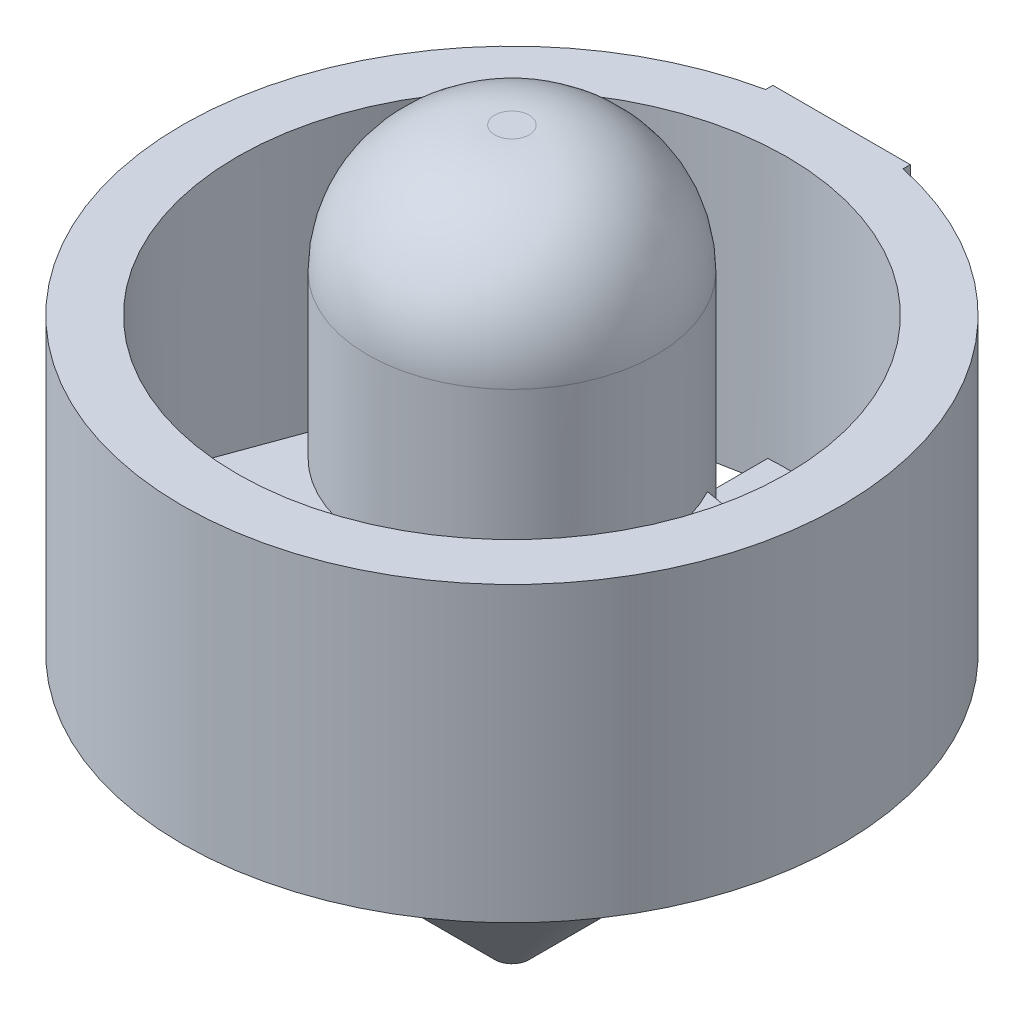
SolidWorks part; units mm, degrees
ref_plane "Front Plane" through (0, 0, 0) normal (0, 0, 1) x (1, 0, 0)
ref_plane "Top Plane" through (0, 0, 0) normal (0, 1, 0) x (1, 0, 0)
ref_plane "Right Plane" through (0, 0, 0) normal (1, 0, 0) x (0, 0, -1)
sketch "Sketch1" plane through (0, 0, 0) normal (0, 1, 0) x (1, 0, 0)
  circle A0 centre (0, 0) radius 45.72
  circle A1 centre (0, 0) radius 38.1
  circle A2 centre (0, 0) radius 20.0025
  dimension "D1" = 91.44
  dimension "D2" = 76.2
  dimension "D3" = 40.005
extrude "Boss-Extrude1" add sketch "Sketch1" along normal blind 20.32 and the other way blind 20.32 contours A0 A1 region at (-44.4268, 0, 0)
extrude "Boss-Extrude2" add sketch "Sketch1<4>" along normal blind 43.18 and the other way blind 55.88 separate body contours A2
sketch "Sketch1<4>" plane through (0, 0, 0) normal (0, 1, 0) x (1, 0, 0) same geometry as "Sketch1"
chamfer "Chamfer1" distance 17.62 angle 45 1 edges at (0, -55.88, 20.0025)
fillet "Fillet1" radius 17.62 1 edges at (0, 43.18, 20.0025)
sketch "Sketch2" plane through (0, 0, 0) normal (0, 1, 0) x (1, 0, 0)
  line L0 (17.589, 9.525) -> (35.369, 6.3899)
  line L1 (35.369, 6.3899) -> (35.369, -6.3899)
  line L2 (35.369, -6.3899) -> (17.589, -9.525)
  line L3 (0, 0) -> (35.369, 0) construction
  line L4 (17.589, -9.525) -> (17.589, 0)
  line L5 (17.589, 0) -> (17.589, 9.525)
  line L6 (-23.2183, -27.4355) -> (-17.0434, -10.4701)
  line L7 (-17.0434, -10.4701) -> (-8.7945, -15.2326)
  line L8 (-8.7945, -15.2326) -> (-0.5456, -19.9951)
  line L9 (-0.5456, -19.9951) -> (-12.1507, -33.8254)
  line L10 (-12.1507, -33.8254) -> (-23.2183, -27.4355)
  line L11 (-12.1507, 33.8254) -> (-0.5456, 19.9951)
  line L12 (-0.5456, 19.9951) -> (-8.7945, 15.2326)
  line L13 (-8.7945, 15.2326) -> (-17.0434, 10.4701)
  line L14 (-17.0434, 10.4701) -> (-23.2183, 27.4355)
  line L15 (-23.2183, 27.4355) -> (-12.1507, 33.8254)
  circle A0 centre (0, 0) radius 20.0025 construction
  point P11 (0, 0)
  point P12 (-17.0434, -10.4701)
  point P22 (0, 0)
  dimension "D1" = 17.78
  dimension "D2" = 100
  dimension "D3" = 9.525
  dimension "D4" = 3
extrude "Boss-Extrude3" add sketch "Sketch2" along normal blind 3.175
sketch "Sketch3" plane through (0, -20.32, 0) normal (0, -1, 0) x (1, 0, 0)
  line L0 (38.1, 0) -> (0, 0) construction
  line L1 (38.1, 2.54) -> (0, 2.54)
  line L2 (38.1, -2.54) -> (0, -2.54)
  line L3 (-2.54, -38.1) -> (-2.54, 0)
  line L4 (2.54, -38.1) -> (2.54, 0)
  line L5 (-38.1, 2.54) -> (0, 2.54)
  line L6 (-38.1, -2.54) -> (0, -2.54)
  line L7 (2.54, 38.1) -> (2.54, 0)
  line L8 (-2.54, 38.1) -> (-2.54, 0)
  circle A0 centre (0, 0) radius 38.1 construction
  arc A1 (38.1, 2.54) -> (38.1, -2.54) centre (38.1, 0) cw
  arc A2 (0, 2.54) -> (0, -2.54) centre (0, 0) ccw
  arc A3 (2.54, -38.1) -> (-2.54, -38.1) centre (0, -38.1) cw
  arc A4 (2.54, 0) -> (-2.54, 0) centre (0, 0) ccw
  arc A5 (-38.1, -2.54) -> (-38.1, 2.54) centre (-38.1, 0) cw
  arc A6 (0, -2.54) -> (0, 2.54) centre (0, 0) ccw
  arc A7 (-2.54, 38.1) -> (2.54, 38.1) centre (0, 38.1) cw
  arc A8 (-2.54, 0) -> (2.54, 0) centre (0, 0) ccw
  point P26 (0, 0)
  circle M2 centre (0, 0) radius 38.1
  dimension "D1" = 2.54
  dimension "D2" = 2.54
  dimension "D3" = 4
extrude "Boss-Extrude4" add sketch "Sketch3" against normal blind 3.175 contours L8 L5 L1 L7 M2 | L0 L4 L2 M2 | L0 L1 L7 M2 | L6 L3 L4 L2 M2 | L8 L5 L6 L3 M2 region at (20.3059, -20.32, -1.2695) region at (20.3059, -20.32, 1.2695) region at (0, -20.32, -20.3059) region at (0, -20.32, 20.3059) region at (-20.3059, -20.32, 0)
ref_plane "Plane1" through (0, 0, -45.72) normal (0, 0, -1) x (-1, 0, 0)
sketch "Sketch4" plane through (0, 0, -45.72) normal (0, 0, -1) x (-1, 0, 0)
  line L0 (-45.72, -20.32) -> (45.72, -20.32) construction
  line L1 (-9.525, 20.32) -> (9.525, 20.32)
  line L2 (-9.525, 20.32) -> (-9.525, -20.32)
  line L3 (-9.525, -20.32) -> (9.525, -20.32)
  line L4 (9.525, 20.32) -> (9.525, -20.32)
  line L5 (-9.525, 20.32) -> (9.525, -20.32) construction
  line L6 (-9.525, -20.32) -> (9.525, 20.32) construction
  point P0 (0, 0)
  dimension "D1" = 19.05
extrude "Boss-Extrude5" add sketch "Sketch4" against normal blind 3.175
